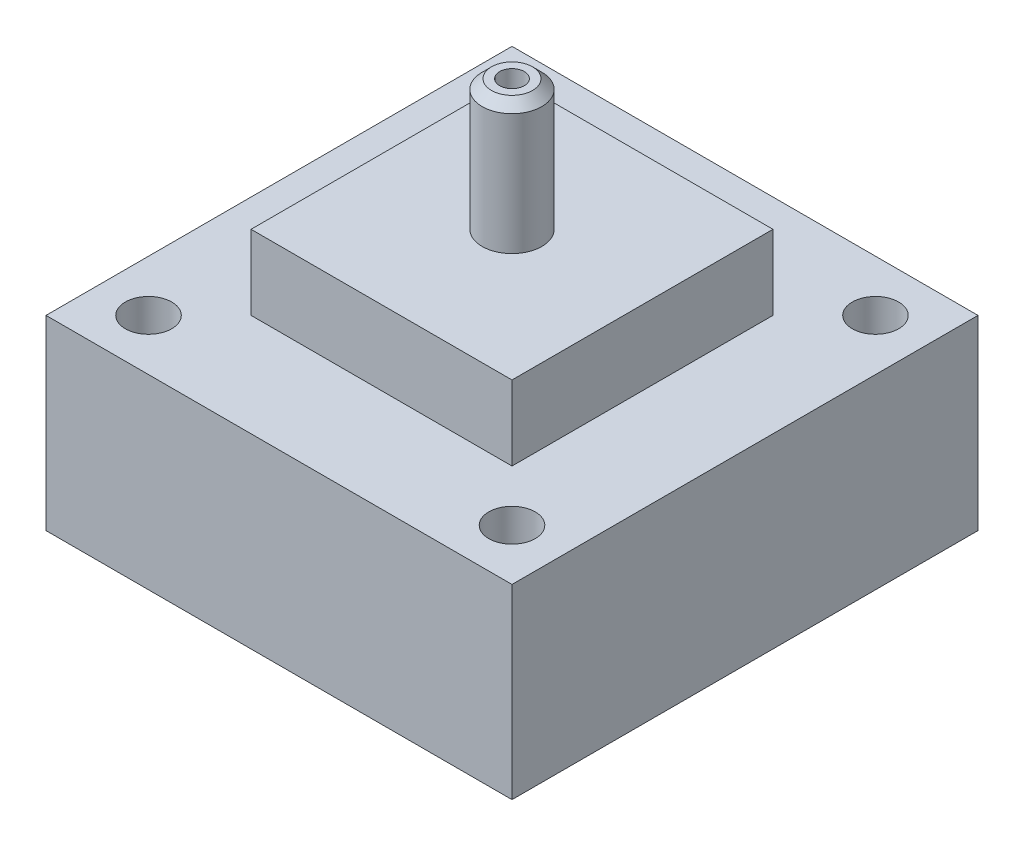
SolidWorks part; units mm, degrees
other "Markup2"
sketch "Sketch7" plane through (-12.5, 11, 12.5) normal (-0.3501, 0.7717, 0.531) x (0.0642, -0.5457, 0.8355)
other "DetailItem2"
material "6061-T6 (SS)"
ref_plane "Front Plane" through (0, 0, 0) normal (0, 0, 1) x (1, 0, 0)
ref_plane "Top Plane" through (0, 0, 0) normal (0, 1, 0) x (1, 0, 0)
ref_plane "Right Plane" through (0, 0, 0) normal (1, 0, 0) x (0, 0, -1)
sketch "Sketch1" plane through (0, 0, 0) normal (0, 1, 0) x (1, 0, 0)
  line L0 (-7, -7) -> (7, -7)
  line L1 (-7, -7) -> (-7, 7)
  line L2 (7, -7) -> (7, 7)
  line L3 (-7, 7) -> (7, 7)
  line L4 (-7, -7) -> (7, 7) construction
  line L5 (7, -7) -> (-7, 7) construction
  point P1 (0, 0)
  dimension "D1" = 14
extrude "Boss-Extrude1" add sketch "Sketch1" along normal blind 4
sketch "Sketch2" plane through (0, 0, 0) normal (0, -1, 0) x (1, 0, 0)
  line L0 (-12.5, -12.5) -> (-12.5, 12.5)
  line L1 (-12.5, -12.5) -> (12.5, -12.5)
  line L2 (-12.5, 12.5) -> (12.5, 12.5)
  line L3 (12.5, -12.5) -> (12.5, 12.5)
  line L4 (-12.5, -12.5) -> (12.5, 12.5) construction
  line L5 (-12.5, 12.5) -> (12.5, -12.5) construction
  line L6 (-0.1744, 7) -> (-0.1744, 12.5) construction
  line L7 (-7, 7) -> (7, 7) construction
  circle A0 centre (-9.75, 9.75) radius 1.2446
  circle A1 centre (9.75, 9.75) radius 1.2446
  circle A2 centre (9.75, -9.75) radius 1.2446
  circle A3 centre (-9.75, -9.75) radius 1.2446
  point P1 (0, 0)
  point P13 (-0.1744, 9.75)
  point P17 (0, 0)
  point P20 (0, 0)
  point P23 (0, 0)
  point P25 (0, 0)
  dimension "D2" = 2.4892
  dimension "D1" = 25
  dimension "D3" = 4
extrude "Boss-Extrude2" add sketch "Sketch2" along normal blind 10
sketch "Sketch3" plane through (0, -10, 0) normal (0, -1, 0) x (1, 0, 0)
  line L0 (-12.5, 12.5) -> (12.5, -12.5) construction
  circle A0 centre (0, 0) radius 4.23
  dimension "D1" = 8.46
extrude "Cut-Extrude1" cut sketch "Sketch3" against normal blind 9.8
sketch "Sketch4" plane through (0, 0, 0) normal (1, 0, 0) x (0, 0, -1)
  line L0 (0, 4) -> (0, 6.6565) construction
  line L1 (-7, 4) -> (7, 4) construction
  line L2 (0.6604, 11) -> (0.6604, 4)
  line L3 (0.6604, 4) -> (1.6, 4)
  line L4 (1.6, 4) -> (1.6, 10.5)
  line L5 (1.6, 10.5) -> (1.1, 11)
  line L6 (1.1, 11) -> (0.6604, 11)
  dimension "D1" = 7
  dimension "D2" = 1.6
  dimension "D3" = 45
  dimension "D4" = 0.5
  dimension "D5" = 0.6604
revolve "Revolve1" add sketch "Sketch4" angle 360 about L0
sketch "Sketch5" plane through (0, 4, 0) normal (0, 1, 0) x (1, 0, 0)
  circle A0 centre (0, 0) radius 0.6604
extrude "Cut-Extrude2" cut sketch "Sketch5" against normal up to surface (14 mm away) up to face at (0, -10, -4.23)
